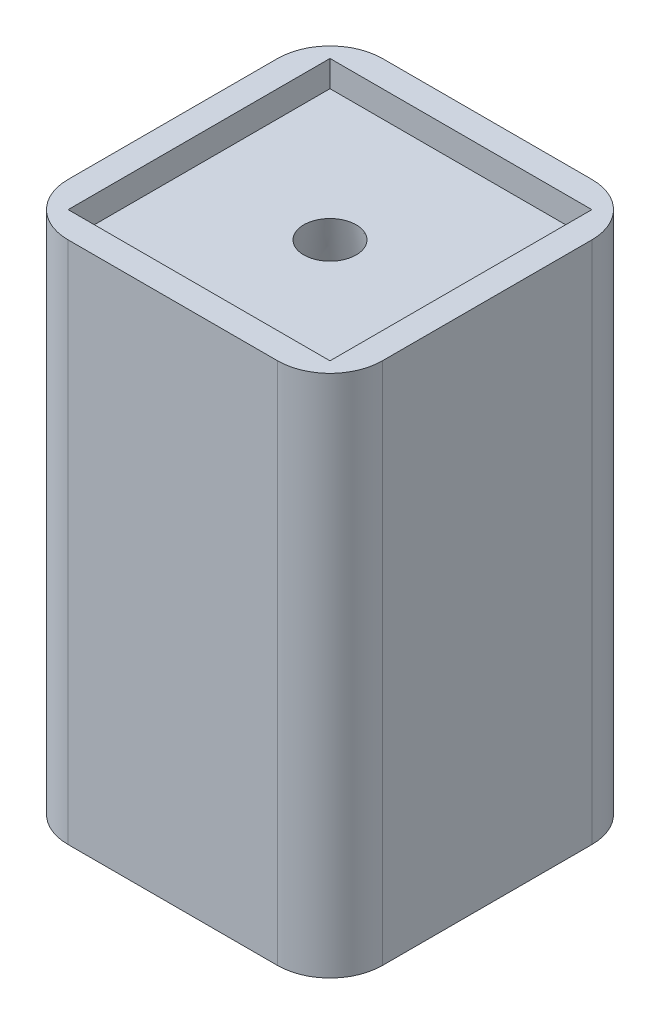
SolidWorks part; units mm, degrees
ref_plane "Front Plane" through (0, 0, 0) normal (0, 0, 1) x (1, 0, 0)
ref_plane "Top Plane" through (0, 0, 0) normal (0, 1, 0) x (1, 0, 0)
ref_plane "Right Plane" through (0, 0, 0) normal (1, 0, 0) x (0, 0, -1)
sketch "Sketch2" plane through (0, 0, 0) normal (0, 1, 0) x (1, 0, 0)
  line L1 (-15, -15) -> (15, -15)
  line L2 (-15, -15) -> (-15, 15)
  line L3 (-15, 15) -> (15, 15)
  line L4 (15, -15) -> (15, 15)
  line L5 (0, 15) -> (0, -15) construction
  line L6 (-15, 0) -> (15, 0) construction
  point P0 (0, 0)
  dimension "D1" = 30
  dimension "D2" = 30
extrude "Boss-Extrude1" add sketch "Sketch2" along normal blind 50
sketch "Sketch3" plane through (0, 50, 0) normal (0, 1, 0) x (1, 0, 0)
  line L1 (-12.5, -12.5) -> (12.5, -12.5)
  line L2 (-12.5, -12.5) -> (-12.5, 12.5)
  line L3 (-12.5, 12.5) -> (12.5, 12.5)
  line L4 (12.5, -12.5) -> (12.5, 12.5)
  line L5 (0, 12.5) -> (0, -12.5) construction
  line L6 (-12.5, 0) -> (12.5, 0) construction
  point P0 (0, 0)
  dimension "D1" = 25
  dimension "D2" = 25
extrude "Cut-Extrude1" cut sketch "Sketch3" against normal blind 2.5
fillet "Fillet1" radius 5 4 edges at (15, 25, 15) (15, 25, -15) (-15, 25, -15) (-15, 25, 15)
sketch "Sketch6" plane through (0, 0, 0) normal (0, -1, 0) x (1, 0, 0)
  circle A0 centre (0, 0) radius 12.5
  dimension "D1" = 25
sketch "Sketch8" plane through (0, 47.5, 0) normal (0, 1, 0) x (1, 0, 0)
  circle A0 centre (0, 0) radius 2.5
  dimension "D1" = 5
loft "Cut-Loft2" cut profiles "Sketch6", "Sketch8" connector at (0, 0, -12.5) connector at (0.7845, 47.5, -2.3737)
ref_plane "Plane1" through (0, 0, 0) normal (-1, 0, 0) x (0, 0, 1)
sketch "Sketch9" plane through (0, 0, 0) normal (-1, 0, 0) x (0, 0, 1)
  line L0 (15, 41) -> (12, 33)
  line L1 (15, 50) -> (15, 0) construction
  line L2 (12, 33) -> (15, 25)
  line L4 (15, 41) -> (15, 25)
  dimension "D1" = 8
  dimension "D2" = 8
  dimension "D3" = 3
